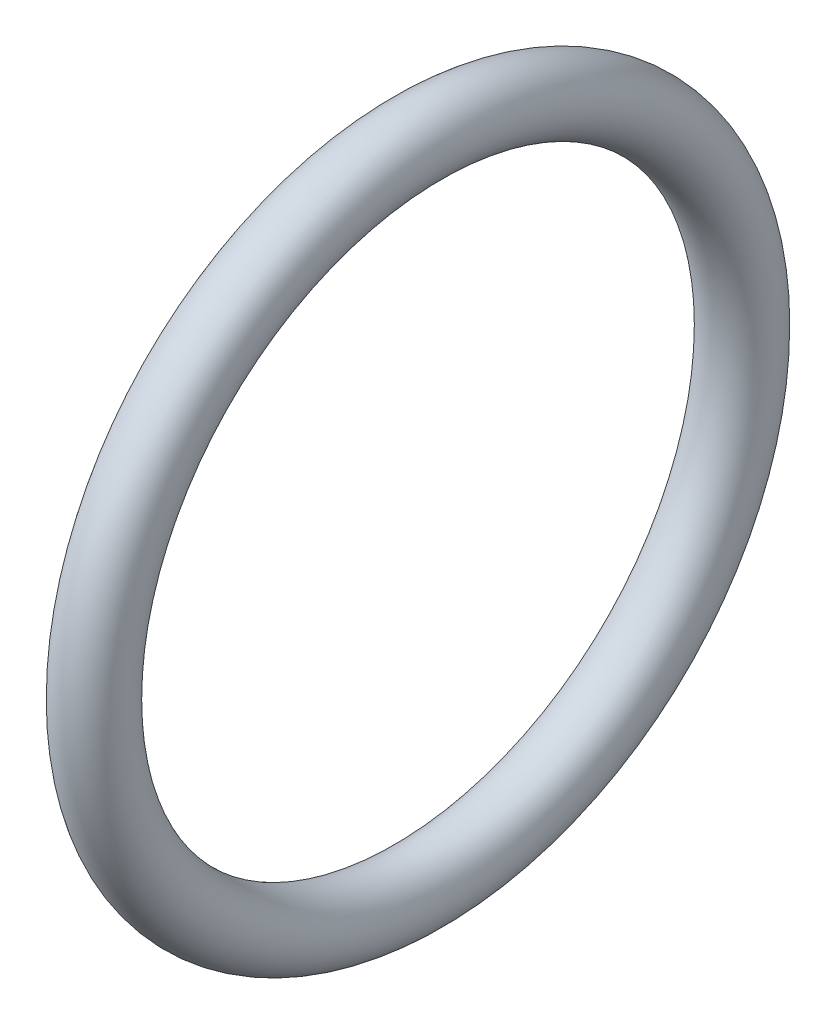
SolidWorks part; units mm, degrees
ref_plane "Plan de face" through (0, 0, 0) normal (0, 0, 1) x (1, 0, 0)
ref_plane "Plan de dessus" through (0, 0, 0) normal (0, 1, 0) x (1, 0, 0)
ref_plane "Plan de droite" through (0, 0, 0) normal (1, 0, 0) x (0, 0, -1)
sketch "Esquisse1" plane through (0, 0, 0) normal (0, 0, 1) x (1, 0, 0)
  line L0 (0, 21.5) -> (0, 26.5) construction
  line L2 (0, 0) -> (-4.9593, 0) construction
  circle A0 centre (0, 24) radius 2.5
  dimension "D1" = 5
  dimension "D2" = 26.5
  dimension "D3" = 21.5
revolve "Révolution1" add sketch "Esquisse1" angle 360 about L2
ref_axis "Axe1" through (-5.3322, 0, 0) along (1, 0, 0)
ref_plane "Plan1" through (0, 25, 0) normal (0, 1, 0) x (1, 0, 0)
